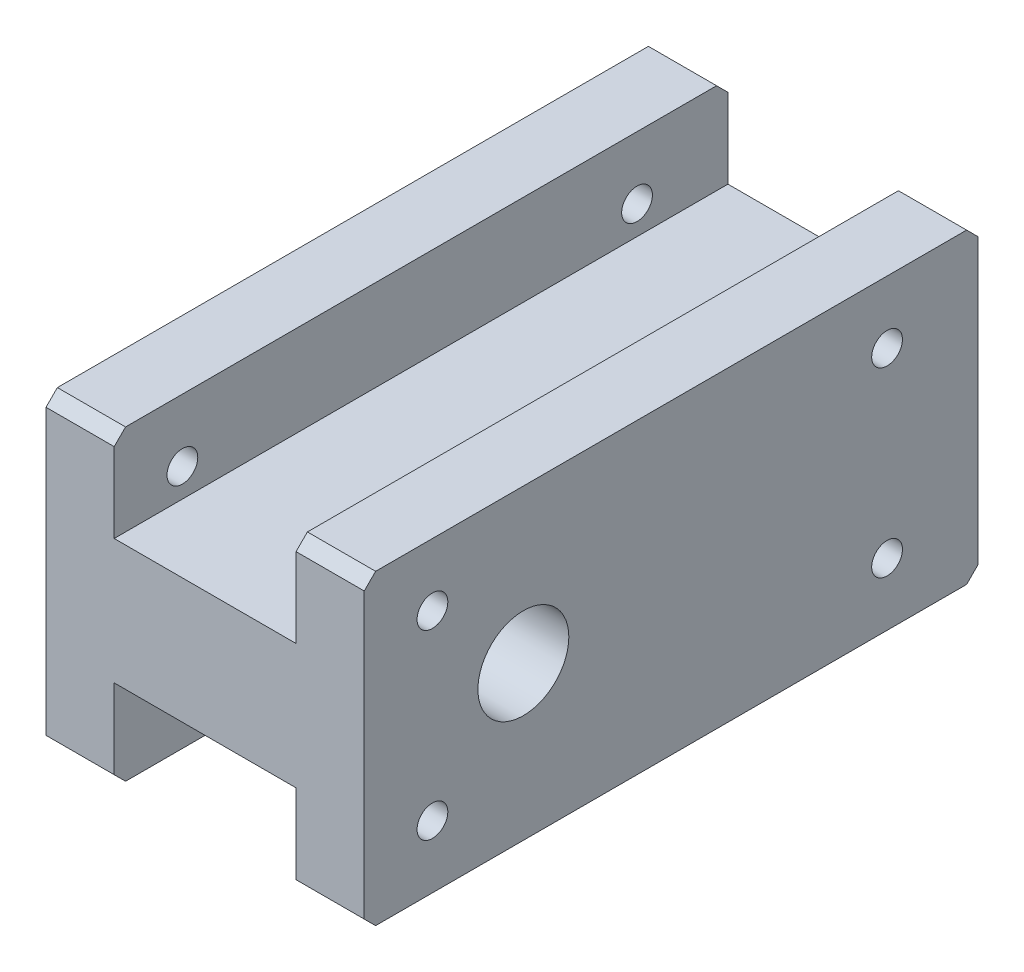
SolidWorks part; units mm, degrees
material "6061-T6 (SS)"
ref_plane "Front Plane" through (0, 0, 0) normal (0, 0, 1) x (1, 0, 0)
ref_plane "Top Plane" through (0, 0, 0) normal (0, 1, 0) x (1, 0, 0)
ref_plane "Right Plane" through (0, 0, 0) normal (1, 0, 0) x (0, 0, -1)
sketch "Sketch1" plane through (0, 0, 0) normal (1, 0, 0) x (0, 0, -1)
  line L1 (-14, 13.5) -> (40, 13.5)
  line L2 (-14, 13.5) -> (-14, -13.5)
  line L3 (-14, -13.5) -> (40, -13.5)
  line L4 (40, 13.5) -> (40, -13.5)
  line L5 (-8, 8) -> (32, 8) construction
  line L6 (-8, 8) -> (-8, -8) construction
  line L7 (-8, -8) -> (32, -8) construction
  line L8 (32, 8) -> (32, -8) construction
  circle A0 centre (0, 0) radius 4
  point P8 (-8, 0)
  dimension "D1" = 8
  dimension "D2" = 13.5
  dimension "D3" = 14
  dimension "D6" = 8
  dimension "D4" = 13.5
  dimension "D5" = 8
  dimension "D7" = 40
  dimension "D8" = 8
extrude "Boss-Extrude1" add sketch "Sketch1" against normal blind 28
hole_wizard "#6-32 Tapped Hole1" positions "Sketch2" profile "Sketch3" tap size "#6-32" standard "ANSI Inch" end condition through all
sketch "Sketch2" plane through (0, 0, 0) normal (1, 0, 0) x (0, 0, -1)
  point P0 (-8, 8)
  point P3 (-8, -8)
  point P6 (32, -8)
  point P9 (32, 8)
sketch "Sketch3" plane through (0, 8, 8) normal (0, 1, 0) x (0, 0, -1)
  line L0 (0, 0) -> (0, 28)
  line L1 (0, 28) -> (1.3525, 28)
  line L2 (1.3525, 28) -> (1.3525, 0)
  line L5 (1.3525, 0) -> (0, 0)
  line L11 (0, -6.35) -> (0, 107.95) construction
  dimension "Thread Major Dia." = 2.7051
  dimension "Thru Tap Drill Depth" = 28
sketch "Sketch4" plane through (0, 0, 14) normal (0, 0, 1) x (1, 0, 0)
  line L0 (-28, 13.5) -> (0, 13.5) construction
  line L1 (-22, 13.5) -> (-6, 13.5)
  line L2 (-22, 13.5) -> (-22, 5.5)
  line L3 (-22, 5.5) -> (-6, 5.5)
  line L4 (-6, 13.5) -> (-6, 5.5)
  line L5 (0, 13.5) -> (0, -13.5) construction
  line L6 (-28, 13.5) -> (-28, -13.5) construction
  line L7 (-28, -13.5) -> (0, -13.5) construction
  line L8 (-22, -13.5) -> (-6, -13.5)
  line L9 (-22, -13.5) -> (-22, -5.5)
  line L10 (-22, -5.5) -> (-6, -5.5)
  line L11 (-6, -13.5) -> (-6, -5.5)
  dimension "D1" = 6
  dimension "D2" = 6
  dimension "D3" = 11
extrude "Cut-Extrude1" cut sketch "Sketch4" against normal through all
chamfer "Chamfer1" distance 1 angle 45 8 edges at (-25, -13.5, -40) (-3, -13.5, -40) (-3, -13.5, 14) (-25, -13.5, 14) (-3, 13.5, -40) (-25, 13.5, -40) (-3, 13.5, 14) (-25, 13.5, 14)
